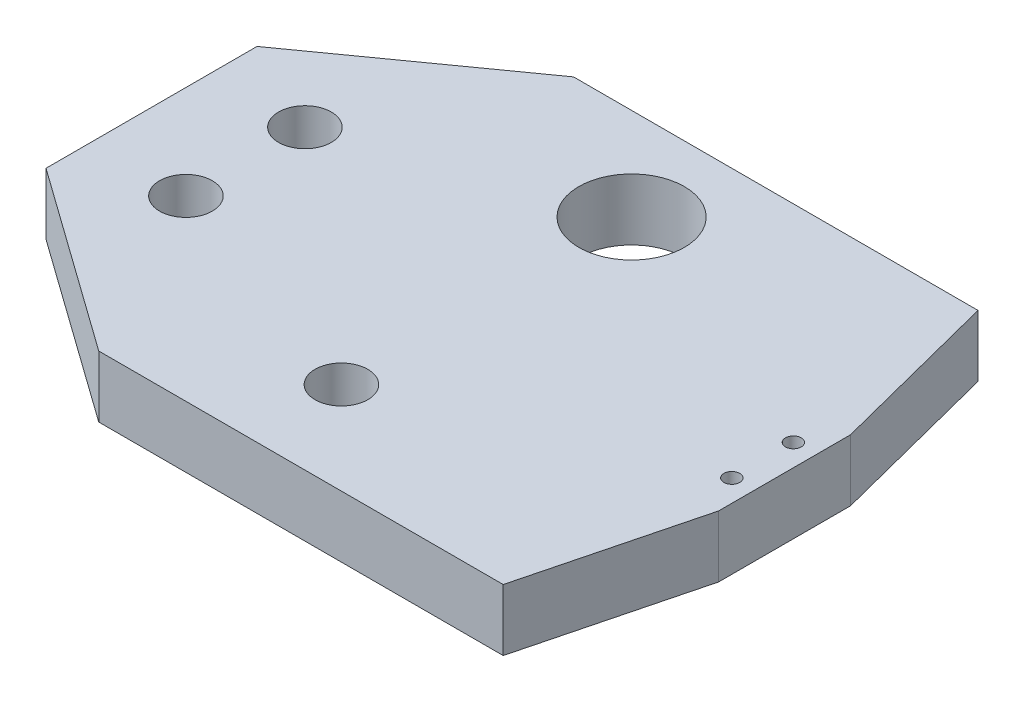
SolidWorks part; units mm, degrees
ref_plane "Front" through (0, 0, 0) normal (0, 0, 1) x (1, 0, 0)
ref_plane "Top" through (0, 0, 0) normal (0, 1, 0) x (1, 0, 0)
ref_plane "Right" through (0, 0, 0) normal (1, 0, 0) x (0, 0, -1)
sketch "Sketch2" plane through (0, 0, 0) normal (0, 1, 0) x (1, 0, 0)
  line L0 (-99.8257, 0) -> (96.2886, 0) construction
  line L1 (-99.8257, 0) -> (-351.8104, 0) construction
  line L3 (-170, -90) -> (-50, -90)
  line L4 (-50, 90) -> (-50, -90)
  line L6 (-170, 90) -> (-50, 90)
  line L8 (-240, 40) -> (-240, -40)
  line L9 (-240, -40) -> (-170, -90)
  line L10 (-240, 40) -> (-170, 90)
  point P2 (-240, 0)
  point P12 (-220, 0)
  dimension "D3" = 90
  dimension "D1" = 80
  dimension "D2" = 220
  dimension "D4" = 240
  dimension "D5" = 120
  dimension "D6" = 90
  dimension "D7" = 0
extrude "Boss-Extrude1" add sketch "Sketch2" along normal blind 23.3333
hole_wizard "Ø20.0mm 맞춤핀 구멍1" positions "Sketch4" profile "Sketch3" hole size "Ø20.0" standard "Ansi Metric" end condition through all
sketch "Sketch4" plane through (0, 23.3333, 0) normal (0, 1, 0) x (1, 0, 0)
  line L0 (-27.032, 0) -> (49.1627, 0) construction
  point P30 (-204.3892, 22.5574)
  point P32 (-204.3892, -22.5574)
  point P37 (-112.9963, 55)
  point P39 (-112.9963, -55)
  point P40 (-204.3892, 22.5574)
  dimension "D1" = 110
sketch "Sketch3" plane through (-204.3892, 23.3333, -22.5574) normal (1, 0, 0) x (0, 0, 1)
  line L0 (0, 0) -> (0, 23.3333)
  line L1 (0, 23.3333) -> (10, 23.3333)
  line L2 (10, 23.3333) -> (10, 0)
  line L5 (10, 0) -> (0, 0)
  line L11 (0, -6.35) -> (0, 107.95) construction
  dimension "Thru Hole Dia." = 20
  dimension "Thru Hole Depth" = 23.3333
sketch "Sketch5" plane through (-50, 0, 0) normal (1, 0, 0) x (0, 0, -1)
  line L0 (-90, 23.3333) -> (90, 23.3333) construction
  line L1 (-90, 23.3333) -> (-55, 23.3333)
  line L2 (-90, 23.3333) -> (-90, 53.3333)
  line L3 (-90, 53.3333) -> (-55, 23.3333)
  line L4 (90, 53.3333) -> (90, 23.3333)
  line L5 (90, 53.3333) -> (55, 23.3333)
  line L6 (55, 23.3333) -> (90, 23.3333)
  dimension "D1" = 35
  dimension "D2" = 30
  dimension "D3" = 35
  dimension "D4" = 30
scale "축척1" scale about centroid uniform scaling yes scale factor 0.3
sketch "스케치1" plane through (0, 15.1667, 0) normal (0, 1, 0) x (1, 0, 0)
  line L0 (-95.1275, -7.5) -> (-100.1275, -27)
  line L1 (-136.5435, 27) -> (-83.5353, 27) construction
  line L2 (-110.1275, -27) -> (-100.1275, -27)
  line L3 (-110.1275, -27) -> (-110.1275, 27)
  line L4 (-110.1275, 27) -> (-100.1275, 27)
  line L6 (-110.1275, 27) -> (-146.1275, 27) construction
  line L7 (-95.1275, 7.5) -> (-100.1275, 27)
  line L11 (-95.1275, -7.5) -> (-95.1275, 7.5)
  circle A0 centre (-129.0264, 16.5) radius 22.5 construction
  dimension "D1" = 0
  dimension "D2" = 10
extrude "보스-돌출1" add sketch "스케치1" against normal up to surface (7 mm away) up to face at (-156.4443, 8.1667, 9.7672)
sketch "스케치2" plane through (0, 15.1667, 0) normal (0, 1, 0) x (1, 0, 0)
  circle A0 centre (-129.0264, 16.5) radius 22.5
  dimension "D1" = 45
sketch "스케치3" plane through (0, 8.1667, 0) normal (0, -1, 0) x (1, 0, 0)
  line L0 (-95.1275, 7.3181) -> (-95.1275, -7.5) construction
  line L1 (-95.1275, 7.5) -> (-95.1275, -7.5) construction
  line L2 (-95.1275, -7.5) -> (-100.1275, -7.5) construction
  line L3 (-100.1275, -7.5) -> (-100.1275, 7.3181) construction
  line L4 (-95.1275, 7.5) -> (-100.1275, 7.5) construction
  circle A0 centre (-97.6275, 3.5) radius 0.9
  circle A1 centre (-97.6275, -3.5) radius 0.9
  dimension "D2" = 1.8
  dimension "D3" = 1.8
  dimension "D5" = 2.5
  dimension "D6" = 4
  dimension "D1" = 5
  dimension "D4" = 2.5
  dimension "D7" = 4
extrude "컷-돌출1" cut sketch "스케치3" against normal through all
sketch "스케치4" plane through (0, 8.1667, 0) normal (0, -1, 0) x (1, 0, 0)
  circle A0 centre (-129.0264, -16.5) radius 6
  dimension "D1" = 12
extrude "컷-돌출2" cut sketch "스케치4" against normal through all
